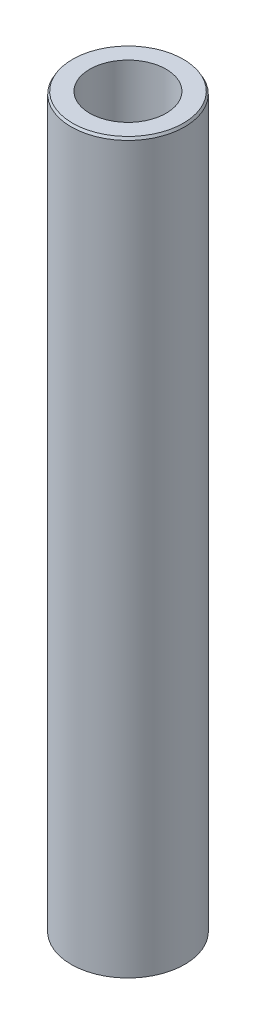
SolidWorks part; units mm, degrees
ref_plane "Front Plane" through (0, 0, 0) normal (0, 0, 1) x (1, 0, 0)
ref_plane "Top Plane" through (0, 0, 0) normal (0, 1, 0) x (1, 0, 0)
ref_plane "Right Plane" through (0, 0, 0) normal (1, 0, 0) x (0, 0, -1)
sketch "Sketch1" plane through (0, 0, 0) normal (0, 1, 0) x (1, 0, 0)
  circle A0 centre (0, 0) radius 27.5
  dimension "SHAFT_OD" = 55
extrude "Boss-Extrude1" add sketch "Sketch1" along normal blind 352.9464
sketch "Sketch2" plane through (0, 0, 0) normal (0, 1, 0) x (1, 0, 0)
  circle A0 centre (0, 0) radius 18.4863
  dimension "BORE_D" = 36.9726
extrude "Cut-Extrude1" cut sketch "Sketch2" along normal through all
chamfer "Chamfer1" distance 1.1924 angle 30 2 edges at (0, 352.9464, 27.5) (0, 0, 27.5) first distance on face at (0, 352.9464, 27.5) first distance on face at (0, 0, 18.4863)
